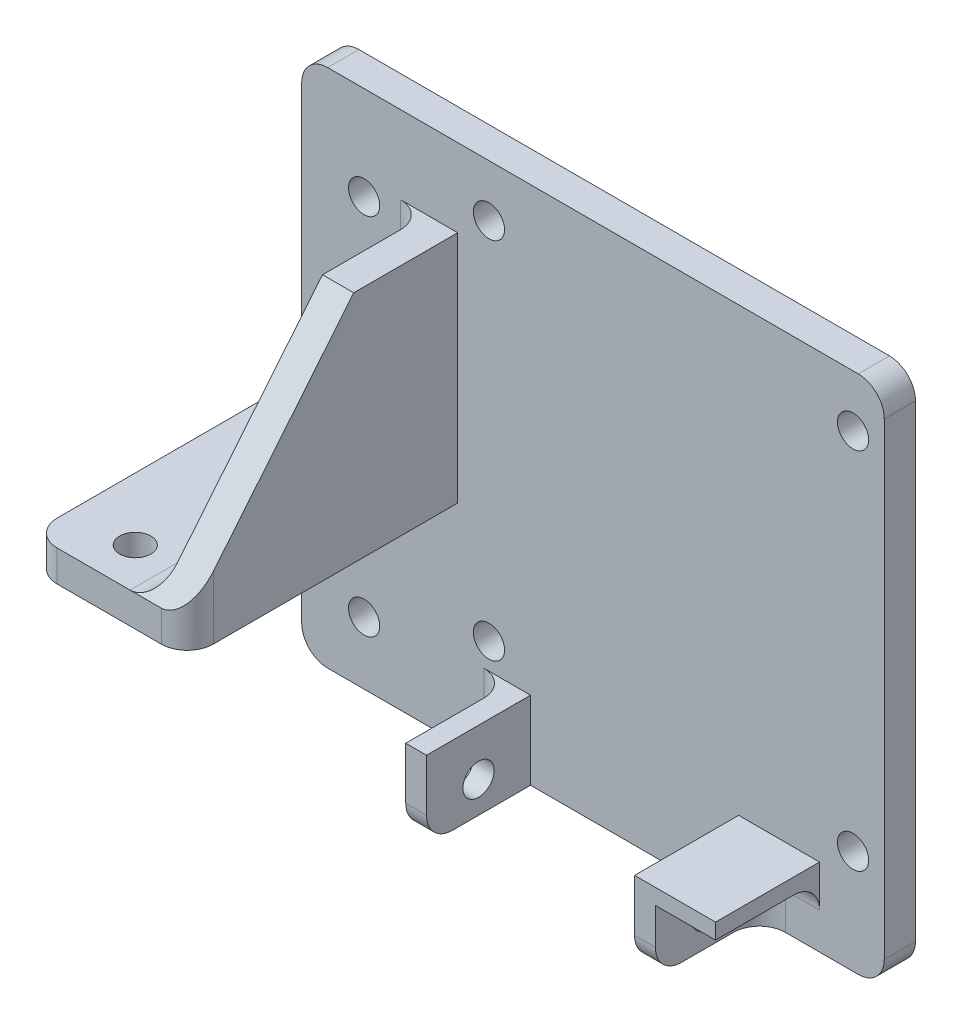
SolidWorks part; units mm, degrees
ref_plane "Front Plane" through (0, 0, 0) normal (0, 0, 1) x (1, 0, 0)
ref_plane "Top Plane" through (0, 0, 0) normal (0, 1, 0) x (1, 0, 0)
ref_plane "Right Plane" through (0, 0, 0) normal (1, 0, 0) x (0, 0, -1)
sketch "Sketch1" plane through (0, 0, 0) normal (0, 0, 1) x (1, 0, 0)
  line L1 (0, 0) -> (56, 0)
  line L2 (0, 0) -> (0, 50)
  line L3 (0, 50) -> (56, 50)
  line L4 (56, 0) -> (56, 50)
  dimension "D1" = 56
  dimension "D2" = 50
extrude "Boss-Extrude1" add sketch "Sketch1" along normal blind 3
sketch "Sketch2" plane through (0, 0, 3) normal (0, 0, 1) x (1, 0, 0)
  line L0 (6, -4.5714) -> (6, 59.5728) construction
  line L1 (18, 10) -> (53, 10) construction
  line L2 (18, 10) -> (18, 45) construction
  line L3 (18, 45) -> (53, 45) construction
  line L4 (53, 10) -> (53, 45) construction
  circle A3 centre (18, 10) radius 1.5
  circle A4 centre (18, 45) radius 1.5
  circle A5 centre (53, 45) radius 1.5
  circle A6 centre (53, 10) radius 1.5
  circle A7 centre (6, 6) radius 1.5
  circle A8 centre (6, 41) radius 1.5
  dimension "D1" = 3
  dimension "D8" = 3
  dimension "D2" = 35
  dimension "D3" = 35
  dimension "D4" = 12
  dimension "D5" = 10
  dimension "D6" = 35
  dimension "D7" = 6
  dimension "D9" = 6
extrude "Cut-Extrude1" cut sketch "Sketch2" against normal through all
sketch "Sketch3" plane through (0, 0, 3) normal (0, 0, 1) x (1, 0, 0)
  line L0 (0, 50) -> (0, 0) construction
  line L1 (0, 20) -> (12, 20)
  line L2 (0, 20) -> (0, 23)
  line L3 (0, 23) -> (12, 23)
  line L4 (12, 20) -> (12, 23)
  dimension "D1" = 3
  dimension "D2" = 12
  dimension "D3" = 20
extrude "Boss-Extrude2" add sketch "Sketch3" along normal blind 26
sketch "Sketch5" plane through (0, 23, 0) normal (0, 1, 0) x (1, 0, 0)
  line L0 (6, -29.5175) -> (6, 3.8156) construction
  line L1 (0, -29) -> (0, -3) construction
  line L5 (56, -3) -> (0, -3) construction
  circle A0 centre (6, -7) radius 1.5
  circle A1 centre (6, -25) radius 1.5
  dimension "D2" = 3
  dimension "D1" = 6
  dimension "D3" = 18
  dimension "D4" = 4
extrude "Cut-Extrude2" cut sketch "Sketch5" against normal blind 10
sketch "Sketch6" plane through (12, 0, 0) normal (1, 0, 0) x (0, 0, -1)
  line L0 (-3, 20) -> (-29, 20)
  line L1 (-29, 20) -> (-29, 23)
  line L3 (-3, 42.5) -> (-3, 20)
  line L5 (-3, 0) -> (-3, 50) construction
  line L6 (-3, 42.5) -> (-13, 42.5)
  line L7 (-13, 42.5) -> (-29, 23)
  line L8 (-3, 50) -> (0, 50) construction
  dimension "D1" = 7.5
  dimension "D2" = 10
extrude "Boss-Extrude3" add sketch "Sketch6" along normal blind 3
sketch "Sketch7" plane through (0, 0, 3) normal (0, 0, 1) x (1, 0, 0)
  line L0 (0, 0) -> (56, 0) construction
  line L1 (20, 0) -> (22, 0)
  line L2 (20, 0) -> (20, 7.5)
  line L4 (22, 0) -> (22, 7.5)
  line L6 (43.9994, 0) -> (42, 0)
  line L7 (43.9994, 0) -> (43.9994, 6)
  line L10 (42, 7.5) -> (49.7818, 7.5)
  line L11 (49.7818, 7.5) -> (49.7818, 6)
  line L12 (49.7818, 6) -> (43.9994, 6)
  line L13 (20, 7.5) -> (22, 7.5)
  line L14 (42, 7.5) -> (42, 0)
  dimension "D1" = 7.5
  dimension "D2" = 7.5
  dimension "D3" = 20
  dimension "D4" = 2
  dimension "D6" = 1.5
extrude "Boss-Extrude4" add sketch "Sketch7" along normal blind 10
sketch "Sketch8" plane through (20, 0, 0) normal (-1, 0, 0) x (0, 0, 1)
  line L0 (3, 3) -> (13, 3) construction
  line L3 (13, 0) -> (3, 0) construction
  line L6 (13, 7.5) -> (13, 0) construction
  circle A0 centre (8, 3) radius 1.5
  dimension "D1" = 3
  dimension "D2" = 3
  dimension "D3" = 5
extrude "Cut-Extrude3" cut sketch "Sketch8" against normal through all
fillet "Fillet1" radius 2.5 4 edges at (0, 50, 1.5) (0, 0, 1.5) (56, 0, 1.5) (56, 50, 1.5)
fillet "Fillet2" radius 2.5 6 edges at (20, 3.75, 3) (12, 23, 16) (12, 32.75, 3) (46.8906, 6, 3) (43.9994, 3, 3) (6, 23, 3)
fillet "Fillet3" radius 2.5 2 edges at (0, 21.5, 29) (15, 21.5, 29)
fillet "Fillet4" radius 2.5 2 edges at (42.9997, 0, 13) (21, 0, 13)
